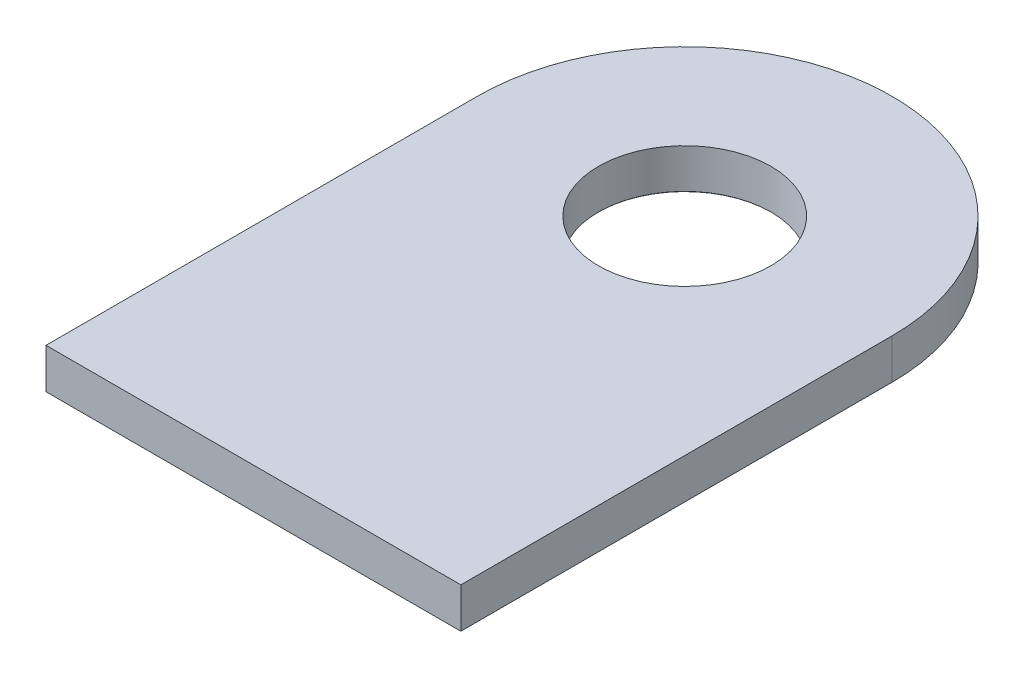
SolidWorks part; units mm, degrees
material "Alloy Steel"
ref_plane "Front Plane" through (0, 0, 0) normal (0, 0, 1) x (1, 0, 0)
ref_plane "Top Plane" through (0, 0, 0) normal (0, 1, 0) x (1, 0, 0)
ref_plane "Right Plane" through (0, 0, 0) normal (1, 0, 0) x (0, 0, -1)
sketch "Sketch1" plane through (0, 0, 0) normal (0, 1, 0) x (1, 0, 0)
  line L0 (-7.94, 0) -> (-7.94, -16.51)
  line L1 (-7.94, -16.51) -> (7.94, -16.51)
  line L2 (7.94, -16.51) -> (7.94, 0)
  circle A0 centre (0, 0) radius 7.94
  dimension "D1" = 15.88
  dimension "D2" = 16.51
extrude "Boss-Extrude1" add sketch "Sketch1" along normal blind 1.54 contours A0 | A0 L0 L1 L2 region at (0, 0, 11.2202) region at (0, 0, 0)
sketch "Sketch4" plane through (0, 0, 0) normal (0, -1, 0) x (-1, 0, 0)
  point P0 (0, 0)
hole_wizard "M6 Clearance Hole1" positions "Sketch4" profile "Sketch3" hole size "M6" standard "ANSI Metric" end condition through all
sketch "Sketch3" plane through (0, 0, 0) normal (1, 0, 0) x (0, 0, -1)
  line L0 (0, 0) -> (0, 1.54)
  line L1 (0, 1.54) -> (3.3, 1.54)
  line L2 (3.3, 1.54) -> (3.3, 0.025)
  line L3 (3.3, 0.025) -> (3.325, 0)
  line L5 (3.325, 0) -> (0, 0)
  line L6 (-3.3, 0.025) -> (-3.325, 0) construction
  line L11 (0, -6.35) -> (0, 107.95) construction
  dimension "Thru Hole Dia." = 6.6
  dimension "Thru Hole Depth" = 1.54
  dimension "Near C'Sink Dia." = 6.65
  dimension "Near C'Sink Angle" = 90
